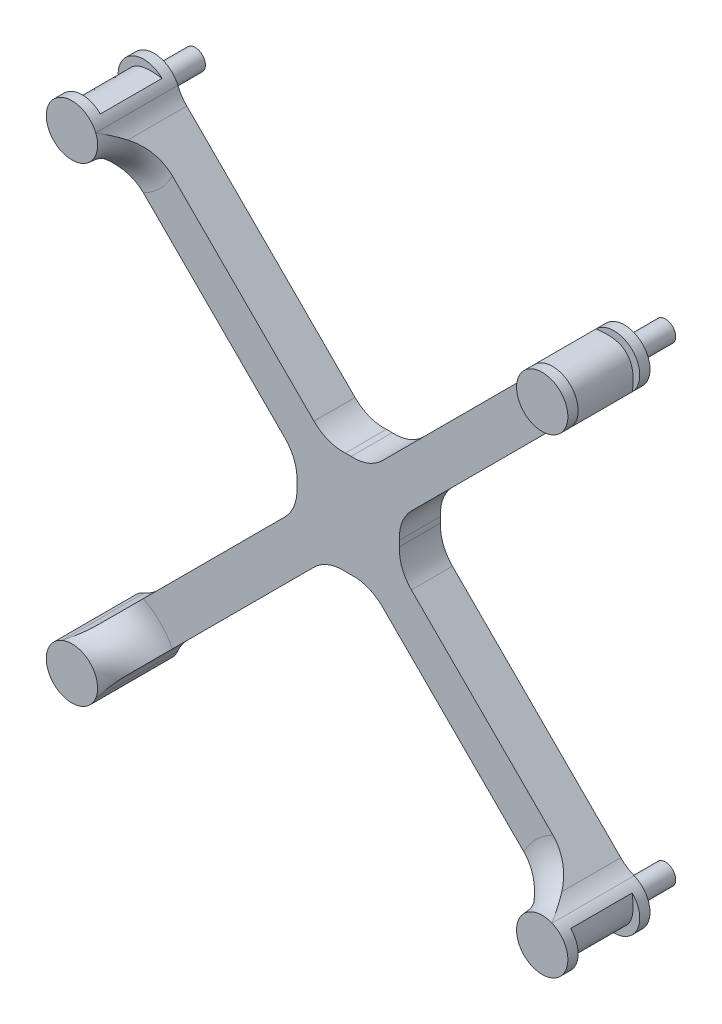
SolidWorks part; units mm, degrees
material "ABS generico"
ref_plane "Piano frontale" through (0, 0, 0) normal (0, 0, 1) x (1, 0, 0)
ref_plane "Piano superiore" through (0, 0, 0) normal (0, 1, 0) x (1, 0, 0)
ref_plane "Piano destro" through (0, 0, 0) normal (1, 0, 0) x (0, 0, -1)
sketch "Schizzo1" plane through (0, 0, 0) normal (0, 0, 1) x (1, 0, 0)
  circle A0 centre (-11.45, 11.45) radius 1.25
  circle A1 centre (11.45, 11.45) radius 1.25
  circle A2 centre (11.45, -11.45) radius 1.25
  circle A3 centre (-11.45, -11.45) radius 1.25
  point P2 (0, 0)
  point P12 (0, 0)
  dimension "D3" = 2.5
  dimension "D1" = 11.45
  dimension "D4" = 11.45
  dimension "D2" = 4
extrude "Estrusione-Estrusione1" add sketch "Schizzo1" along normal blind 4
sketch "Schizzo2" plane through (0, 0, 0) normal (0, 0, 1) x (1, 0, 0)
  circle A0 centre (11.45, 11.45) radius 0.5
  circle A1 centre (11.45, -11.45) radius 0.5
  circle A2 centre (-11.45, -11.45) radius 0.5
  circle A3 centre (-11.45, 11.45) radius 0.5
  point P3 (0, 0)
  point P4 (0, 0)
  point P12 (0, 0)
  dimension "D1" = 1
  dimension "D2" = 4
extrude "Estrusione-Estrusione2" add sketch "Schizzo2" against normal blind 2
sketch "Schizzo4" plane through (0, 0, 0) normal (0, 0, 1) x (1, 0, 0)
  line L0 (0.9131, 2.3273) -> (10.7429, 12.1571)
  line L1 (-0.9131, 2.3273) -> (-10.7429, 12.1571)
  line L2 (-0.9131, -2.3273) -> (-10.7429, -12.1571)
  line L3 (0, 0) -> (0, 6.4321) construction
  line L4 (0, 0) -> (7.6639, 0) construction
  line L5 (2.3273, 0.9131) -> (12.1571, 10.7429)
  line L6 (-2.3273, 0.9131) -> (-12.1571, 10.7429)
  line L7 (2.3273, -0.9131) -> (12.1571, -10.7429)
  line L8 (0.9131, -2.3273) -> (10.7429, -12.1571)
  line L9 (-2.3273, -0.9131) -> (-12.1571, -10.7429)
  line L10 (-10.7429, 12.1571) -> (-12.1571, 10.7429)
  line L11 (10.7429, 12.1571) -> (12.1571, 10.7429)
  line L12 (12.1571, -10.7429) -> (10.7429, -12.1571)
  line L13 (-12.1571, -10.7429) -> (-10.7429, -12.1571)
  circle A0 centre (0, 0) radius 2.5
  dimension "D1" = 5
extrude "Estrusione-Estrusione3" add sketch "Schizzo4" along normal blind 2 contours A0 | A0 L1 L10 L6 | A0 L5 L11 L0 | A0 L8 L12 L7 | A0 L9 L13 L2 region at (6.5846, 6.5846, 0) region at (0, 0, 0) region at (-6.5846, 6.5846, 0) region at (6.5846, -6.5846, 0) region at (-6.5846, -6.5846, 0)
fillet "Raccordo1" radius 2 20 edges at (2.3273, -0.9131, 1) (2.3273, 0.9131, 1) (-0.9131, 2.3273, 1) (0.9131, 2.3273, 1) (-2.3273, 0.9131, 1) (-2.3273, -0.9131, 1) (-0.9131, -2.3273, 1) (0.9131, -2.3273, 1) (-11.6268, -10.2126, 1) (-10.5661, -10.5661, 2) (-10.2126, -11.6268, 1) (11.6268, -10.2126, 1) (10.5661, -10.5661, 2) (10.2126, -11.6268, 1) (10.2126, 11.6268, 1) (11.6268, 10.2126, 1) (10.5661, 10.5661, 2) (-10.5661, 10.5661, 2) (-10.2126, 11.6268, 1) (-11.6268, 10.2126, 1)
ref_plane "Piano1" through (0, 0, 3.5) normal (0, 0, 1) x (1, 0, 0)
sketch "Schizzo5" plane through (0, 0, 3.5) normal (0, 0, 1) x (1, 0, 0)
  line L0 (-11.45, 11.45) -> (-12.7, 12.7) construction
  line L1 (-11.45, 11.45) -> (-10.5661, 12.3339) construction
  line L2 (11.45, 11.45) -> (12.7, 12.7) construction
  line L3 (11.45, 11.45) -> (12.3339, 10.5661) construction
  line L4 (11.45, -11.45) -> (12.7, -12.7) construction
  line L5 (11.45, -11.45) -> (10.5661, -12.3339) construction
  line L6 (-11.45, -11.45) -> (-12.7, -12.7) construction
  line L7 (-11.45, -11.45) -> (-12.3339, -10.5661) construction
  line L8 (0, 0) -> (0, 13.8225) construction
  arc A0 (-10.5661, 12.3339) -> (-12.3339, 10.5661) centre (-11.45, 11.45) ccw
  arc A4 (12.3339, 10.5661) -> (10.5661, 12.3339) centre (11.45, 11.45) ccw
  arc A5 (10.5661, -12.3339) -> (12.3339, -10.5661) centre (11.45, -11.45) ccw
  arc A6 (-12.3339, -10.5661) -> (-10.5661, -12.3339) centre (-11.45, -11.45) ccw
  spline S0 degree 2 poles (-10.5661, 12.3339) (-12.6694, 12.6694) (-12.3339, 10.5661) knots 0 0 0 1 1 1
  spline S1 degree 2 poles (12.3339, 10.5661) (12.6694, 12.6694) (10.5661, 12.3339) knots 0 0 0 1 1 1
  spline S2 degree 2 poles (10.5661, -12.3339) (12.6694, -12.6694) (12.3339, -10.5661) knots 0 0 0 1 1 1
  spline S3 degree 2 poles (-12.3339, -10.5661) (-12.6694, -12.6694) (-10.5661, -12.3339) knots 0 0 0 1 1 1
  point P24 (0, 0)
  point P28 (0, 0)
  dimension "D2" = 45
  dimension "D1" = 4
extrude "Taglio-Estrusione1" cut sketch "Schizzo5" against normal blind 3
